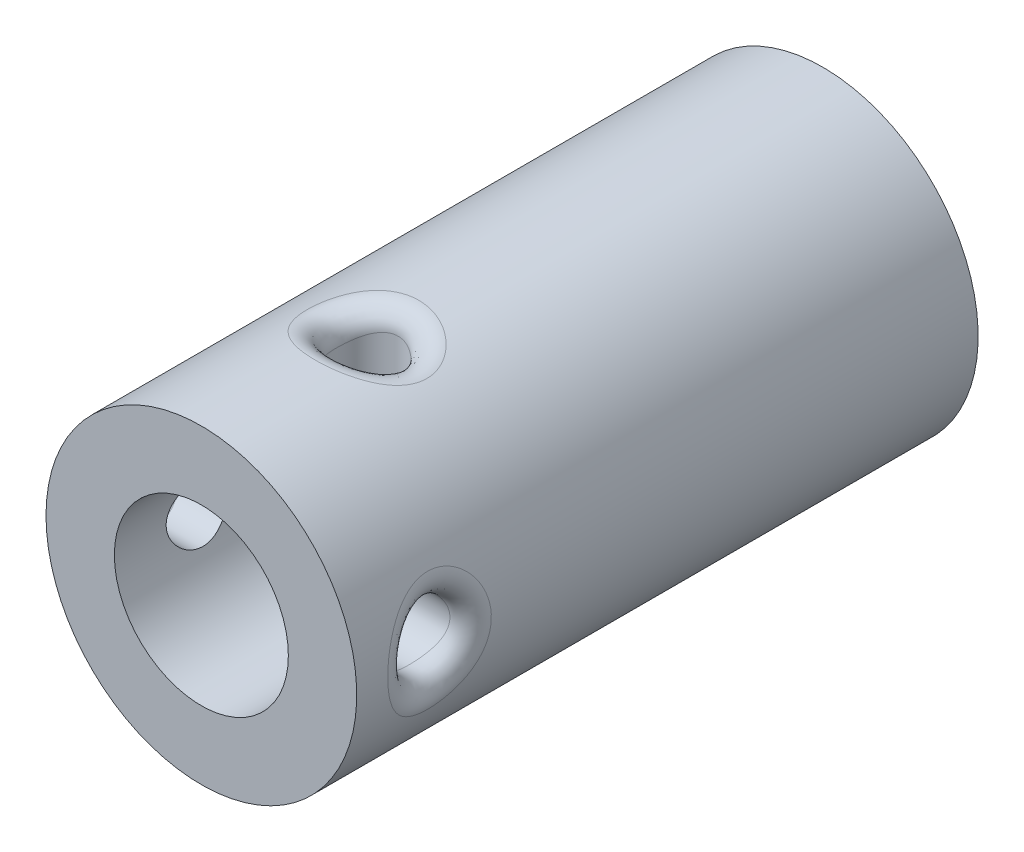
SolidWorks part; units mm, degrees
ref_plane "Front Plane" through (0, 0, 0) normal (0, 0, 1) x (1, 0, 0)
ref_plane "Top Plane" through (0, 0, 0) normal (0, 1, 0) x (1, 0, 0)
ref_plane "Right Plane" through (0, 0, 0) normal (1, 0, 0) x (0, 0, -1)
sketch "Sketch1" plane through (0, 0, 0) normal (0, 0, 1) x (1, 0, 0)
  line L1 (3.6662, -6.35) -> (7.3323, 0)
  line L2 (7.3323, 0) -> (3.6662, 6.35)
  line L3 (3.6662, 6.35) -> (-3.6662, 6.35)
  line L4 (-3.6662, 6.35) -> (-7.3323, 0)
  line L5 (-7.3323, 0) -> (-3.6662, -6.35)
  line L6 (-3.6662, -6.35) -> (3.6662, -6.35)
  circle A0 centre (0, 0) radius 6.35 construction
  dimension "D1" = 12.7
extrude "Boss-Extrude1" add sketch "Sketch1" along normal blind 27
sketch "Sketch2" plane through (0, 0, 0) normal (0, 0, -1) x (-1, 0, 0)
  circle A0 centre (0, 0) radius 4.5
  dimension "D1" = 9
extrude "Boss-Extrude2" add sketch "Sketch2" along normal blind 61
sketch "Sketch3" plane through (0, 0, -61) normal (0, 0, -1) x (-1, 0, 0)
  line L0 (-5, 3.2) -> (-2.7203, 3.2) construction
  line L1 (-2.7203, 3.2) -> (2.7203, 3.2)
  line L2 (-5, 3.2) -> (-5, -3.2) construction
  line L3 (-2.7203, -3.2) -> (2.7203, -3.2)
  line L4 (5, 3.2) -> (5, -3.2) construction
  line L5 (-5, 3.2) -> (5, -3.2) construction
  line L6 (-5, -3.2) -> (5, 3.2) construction
  line L7 (-5, -3.2) -> (-2.7203, -3.2) construction
  line L8 (2.7203, -3.2) -> (5, -3.2) construction
  line L9 (2.7203, 3.2) -> (5, 3.2) construction
  arc A0 (-2.7203, 3.2) -> (-2.7203, -3.2) centre (0, 0) ccw
  arc A1 (2.7203, 3.2) -> (-2.7203, 3.2) centre (0, 0) ccw construction
  arc A2 (-2.7203, -3.2) -> (2.7203, -3.2) centre (0, 0) ccw construction
  arc A3 (2.7203, -3.2) -> (2.7203, 3.2) centre (0, 0) ccw
  point P0 (0, 0)
  dimension "D1" = 8.4
  dimension "D2" = 6.4
  dimension "D3" = 10
extrude "Cut-Extrude1" cut sketch "Sketch3" against normal blind 14
sketch "Sketch4" plane through (0, 0, -61) normal (0, 0, -1) x (-1, 0, 0)
  line L0 (-2.7203, -3.2) -> (2.7203, -3.2) construction
  line L1 (2.7203, 3.2) -> (-2.7203, 3.2) construction
  line L2 (-2.7203, -3.2) -> (2.7203, -3.2)
  line L3 (2.7203, 3.2) -> (-2.7203, 3.2)
  arc A0 (-2.7203, 3.2) -> (-2.7203, -3.2) centre (0, 0) ccw construction
  circle A1 centre (0, 0) radius 4.5
  circle A2 centre (0, 0) radius 4.5 construction
  arc A3 (2.7203, -3.2) -> (2.7203, 3.2) centre (0, 0) ccw construction
  arc A4 (-2.7203, 3.2) -> (-2.7203, -3.2) centre (0, 0) ccw
  arc A5 (2.7203, -3.2) -> (2.7203, 3.2) centre (0, 0) ccw
  circle A6 centre (0, 0) radius 7.5
  dimension "D2" = 15
  dimension "D1" = 0
extrude "Boss-Extrude3" add sketch "Sketch4" against normal blind 30
sketch "Sketch5" plane through (0, 0, 0) normal (0, 0, -1) x (-1, 0, 0)
  circle A0 centre (0, 0) radius 4.5 construction
  circle A1 centre (0, 0) radius 4.5 construction
  circle A2 centre (0, 0) radius 4.2
  dimension "D1" = 0.3
extrude "Cut-Extrude2" cut sketch "Sketch5" along direction (0, 0, 1) on the side against the normal up to surface (58 mm away) from surface at 31 flip side to cut starting at face at (-4.5, 0, -31)
sketch "Sketch6" plane through (0, 1.7015, 0) normal (-1, 0, 0) x (0, 0, 1)
  line L0 (27, -1.7015) -> (22.5, -1.7015) construction
  line L1 (27, -5.9015) -> (27, 2.4985) construction
  circle A0 centre (22.5, -1.7015) radius 1.5
  circle A1 centre (12.5, -1.7015) radius 1.5
  dimension "D2" = 3
  dimension "D3" = 10
  dimension "D1" = 4.5
extrude "Cut-Extrude3" cut sketch "Sketch6" against normal through all both and the other way through all
sketch "Sketch10" plane through (0, 0, 27) normal (0, 0, 1) x (1, 0, 0)
  circle A0 centre (0, 0) radius 4.2
extrude "Cut-Extrude7" cut sketch "Sketch10" against normal up to surface (58 mm away) and the other way through all up to face at (-7.5, 0, -31)
sketch "Sketch8" plane through (0, 0, -31) normal (0, 0, 1) x (1, 0, 0)
  circle A0 centre (0, 0) radius 4.2
  dimension "D1" = 8.4
extrude "Cut-Extrude4" cut sketch "Sketch8" against normal blind 11.5
sketch "Sketch11" plane through (0, 0, 0) normal (0, 1, 0) x (1, 0, 0)
  line L0 (-7.5, 31) -> (7.5, 31) construction
  circle A0 centre (0, 39) radius 1.5
  dimension "D1" = 3
  dimension "D2" = 8
extrude "Cut-Extrude8" cut sketch "Sketch11" against normal through all both and the other way through all
sketch "Sketch12" plane through (0, 0, 0) normal (1, 0, 0) x (0, 0, -1)
  line L0 (31, 7.5) -> (31, -7.5) construction
  circle A0 centre (35, 0) radius 1.5
  dimension "D1" = 3
  dimension "D2" = 4
extrude "Cut-Extrude9" cut sketch "Sketch12" against normal through all both and the other way through all
fillet "Fillet2" radius 1 4 edges at (-7.4935, 0.3117, -33.5327) (7.4935, -0.3117, -33.5327) (0.3117, -7.4935, -40.4673) (-0.3117, 7.4935, -40.4673)
